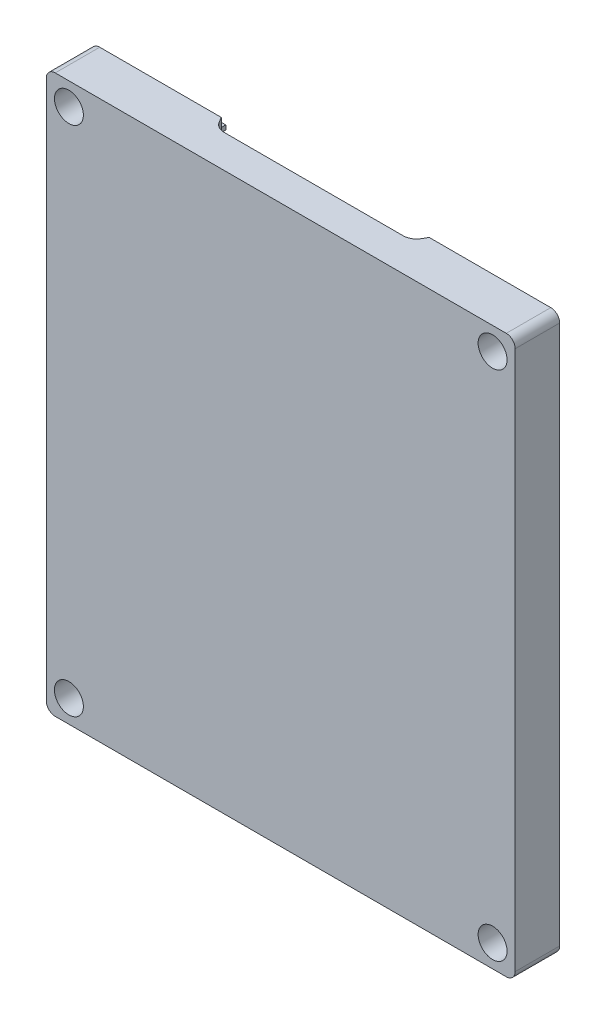
SolidWorks part; units mm, degrees
note: The reader was unsure of these and kept them because the rebuilt part matched: shared geometry of "Esquisse1<5>".
material "ABS"
ref_plane "Plan de face" through (0, 0, 0) normal (0, 0, 1) x (1, 0, 0)
ref_plane "Plan de dessus" through (0, 0, 0) normal (0, 1, 0) x (1, 0, 0)
ref_plane "Plan de droite" through (0, 0, 0) normal (1, 0, 0) x (0, 0, -1)
sketch "Esquisse1" plane through (0, 0, 0) normal (0, 0, 1) x (1, 0, 0)
  line L10 (-50.67, 60.555) -> (50.67, 60.555)
  line L11 (38.72, 58.605) -> (-38.72, 58.605)
  line L12 (-49.72, 46.1908) -> (-38.3058, 57.605)
  line L13 (38.3058, 57.605) -> (-38.3058, 57.605)
  line L14 (38.3058, 57.605) -> (49.72, 46.1908)
  line L15 (49.72, 46.1908) -> (49.72, -50.2908)
  line L21 (49.72, -50.2908) -> (38.3058, -61.705)
  line L26 (38.3058, -61.705) -> (-38.3058, -61.705)
  line L28 (-38.3058, -61.705) -> (-49.72, -50.2908)
  line L48 (-49.72, -50.2908) -> (-49.72, 46.1908)
  line L55 (-23.35, 60.555) -> (-50.67, 60.555)
  line L56 (-52.67, 58.555) -> (-52.67, -62.655)
  line L57 (-50.67, -64.655) -> (50.67, -64.655)
  line L58 (52.67, -62.655) -> (52.67, 58.555)
  line L59 (50.67, 60.555) -> (23.35, 60.555)
  line L64 (23.35, 60.555) -> (23.35, 58.605)
  line L65 (23.35, 58.605) -> (38.72, 58.605)
  line L66 (38.72, 58.605) -> (50.72, 46.605)
  line L67 (50.72, 46.605) -> (50.72, -50.705)
  line L68 (50.72, -50.705) -> (38.72, -62.705)
  line L69 (38.72, -62.705) -> (-38.72, -62.705)
  line L70 (-38.72, -62.705) -> (-50.72, -50.705)
  line L71 (-50.72, -50.705) -> (-50.72, 46.605)
  line L72 (-50.72, 46.605) -> (-38.72, 58.605)
  line L73 (-38.72, 58.605) -> (-23.35, 58.605)
  line L74 (-23.35, 58.605) -> (-23.35, 60.555)
  line L76 (-52.67, 58.555) -> (-52.67, -62.655)
  line L77 (-50.67, -64.655) -> (50.67, -64.655)
  line L78 (52.67, -62.655) -> (52.67, 58.555)
  line L82 (38.72, 58.605) -> (50.72, 46.605)
  line L83 (50.72, 46.605) -> (50.72, -50.705)
  line L84 (50.72, -50.705) -> (38.72, -62.705)
  line L85 (38.72, -62.705) -> (-38.72, -62.705)
  line L86 (-38.72, -62.705) -> (-50.72, -50.705)
  line L87 (-50.72, -50.705) -> (-50.72, 46.605)
  line L88 (-50.72, 46.605) -> (-38.72, 58.605)
  circle A1 centre (-47.5988, -59.5838) radius 1.6 construction
  circle A3 centre (47.5988, -59.5838) radius 1.6 construction
  arc A12 (-50.67, 60.555) -> (-52.67, 58.555) centre (-50.67, 58.555) ccw
  arc A13 (-52.67, -62.655) -> (-50.67, -64.655) centre (-50.67, -62.655) ccw
  arc A18 (50.67, -64.655) -> (52.67, -62.655) centre (50.67, -62.655) ccw
  arc A19 (52.67, 58.555) -> (50.67, 60.555) centre (50.67, 58.555) ccw
  arc A20 (-50.67, 60.555) -> (-52.67, 58.555) centre (-50.67, 58.555) ccw
  arc A21 (-52.67, -62.655) -> (-50.67, -64.655) centre (-50.67, -62.655) ccw
  arc A22 (50.67, -64.655) -> (52.67, -62.655) centre (50.67, -62.655) ccw
  arc A23 (52.67, 58.555) -> (50.67, 60.555) centre (50.67, 58.555) ccw
  circle A25 centre (47.5988, 55.4838) radius 1.6 construction
  circle A27 centre (-47.5988, 55.4838) radius 1.6 construction
  circle A29 centre (-47.5988, -59.5838) radius 1.6
  circle A31 centre (47.5988, -59.5838) radius 1.6
  circle A33 centre (47.5988, 55.4838) radius 1.6
  circle A35 centre (-47.5988, 55.4838) radius 1.6
  dimension "D1" = 0
  dimension "D2" = 1
extrude "Walls" add sketch "Esquisse1" along normal blind 10
extrude "Centrage" add sketch "Esquisse1<5>" against normal blind 1 contours L88 L87 L86 L85 L84 L83 L82 L11 L28 L48 L12 L13 L14 L15 L21 L26
sketch "Esquisse1<5>" plane through (0, 0, 0) normal (0, 0, 1) x (1, 0, 0) same geometry as "Esquisse1"
sketch "Esquisse2" plane through (0, 60.555, 0) normal (0, 1, 0) x (1, 0, 0)
  line L1 (-23.35, -2.6) -> (23.35, -2.6) construction
  line L2 (-23.35, -2.6) -> (-23.35, 1) construction
  line L3 (-23.35, 1) -> (23.35, 1)
  line L4 (23.35, -2.6) -> (23.35, 1) construction
  line L6 (-23.35, 0) -> (-22.72, -1.1)
  line L7 (-38.72, 0) -> (38.72, 0) construction
  line L8 (-23.35, 0) -> (-23.35, 1)
  line L9 (0, -55) -> (0, 55) construction
  line L10 (23.35, 0) -> (22.72, -1.1)
  line L11 (23.35, 0) -> (23.35, 1)
  line L12 (-20.12, -2.6) -> (20.12, -2.6)
  line L13 (-50.67, 0) -> (50.67, 0) construction
  line L20 (38.72, 1) -> (-38.72, 1) construction
  arc A0 (-22.72, -1.1) -> (-20.12, -2.6) centre (-20.1219, 0.4) ccw
  arc A1 (22.72, -1.1) -> (20.12, -2.6) centre (20.1219, 0.4) cw
  point P4 (23.35, 1)
  point P5 (0, 0)
  point P6 (0, -2.6)
  point P22 (0, 0)
  point P23 (0, 0)
  point P24 (23.35, 1)
  point P25 (-23.35, 1)
  point P28 (-23.35, 1)
  point P29 (0, 0)
  point P30 (0, 0)
  point P31 (0, 0)
  point P32 (0, 0)
  point P33 (0, 0)
  point P34 (0, 0)
  point P35 (0, 0)
  point P36 (0, 0)
  point P37 (0, 0)
  point P38 (0, 0)
  point P39 (0, 0)
  dimension "D5" = 3
  dimension "D1" = 46.7
  dimension "D2" = 2.6
  dimension "D3" = 1.1
  dimension "D4" = 0.63
  dimension "D6" = 3.23
extrude "Passage_CMC" cut sketch "Esquisse2" against normal up to next
sketch "Esquisse4" plane through (0, 0, 10) normal (0, 0, 1) x (1, 0, 0)
  line L8 (-49.72, -50.2908) -> (-49.72, 46.1908)
  line L9 (-38.3058, -61.705) -> (-49.72, -50.2908)
  line L10 (38.3058, -61.705) -> (-38.3058, -61.705)
  line L11 (49.72, -50.2908) -> (38.3058, -61.705)
  line L12 (49.72, 46.1908) -> (49.72, -50.2908)
  line L13 (38.3058, 57.605) -> (49.72, 46.1908)
  line L14 (-38.3058, 57.605) -> (38.3058, 57.605)
  line L15 (-49.72, 46.1908) -> (-38.3058, 57.605)
  line L16 (-49.72, -50.2908) -> (-49.72, 46.1908) construction
  line L17 (-49.72, 46.1908) -> (-38.3058, 57.605) construction
  point P3 (38.3058, -61.705)
  point P5 (-38.3058, -61.705)
  point P7 (-49.72, -50.2908)
  point P9 (-49.72, -50.2908)
  point P16 (49.72, -50.2908)
  point P17 (-49.72, 46.1908)
  point P21 (-38.3058, 57.605)
  point P24 (0, 0)
  point P25 (49.72, 46.1908)
  point P27 (49.72, -50.2908)
  point P28 (38.3058, 57.605)
  point P30 (-38.3058, 57.605)
extrude "Couvercle" add sketch "Esquisse4" against normal blind 2
sketch "Esquisse5" plane through (0, 0, 10) normal (0, 0, 1) x (1, 0, 0)
  line L0 (-47.5988, 55.4838) -> (-47.5988, 60.555) construction
  line L2 (-47.5988, 55.4838) -> (-52.67, 55.4838) construction
  line L4 (-47.5988, 55.4838) -> (-44.0129, 51.8979) construction
  line L8 (-49.72, 46.1908) -> (-38.3058, 57.605) construction
  line L9 (-50.67, 60.555) -> (50.67, 60.555) construction
  line L10 (-52.67, 58.555) -> (-52.67, -62.655) construction
  line L11 (-47.5988, -59.5838) -> (-44.0129, -55.9979) construction
  line L12 (-38.3058, -61.705) -> (-49.72, -50.2908) construction
  line L13 (-47.5988, -59.5838) -> (-52.67, -59.5838) construction
  line L14 (-47.5988, -59.5838) -> (-47.5988, -64.655) construction
  line L15 (-50.67, -64.655) -> (50.67, -64.655) construction
  line L16 (0, -55) -> (0, 55) construction
  circle A0 centre (-47.5988, 55.4838) radius 1.6
  circle A5 centre (-47.5988, -59.5838) radius 1.6
  circle A6 centre (47.5988, 55.4838) radius 1.6
  circle A7 centre (47.5988, -59.5838) radius 1.6
  circle A8 centre (-47.5988, -59.5838) radius 3.25
  circle A9 centre (-47.5988, 55.4838) radius 3.25
  circle A10 centre (47.5988, 55.4838) radius 3.25
  circle A11 centre (47.5988, -59.5838) radius 3.25
  dimension "D1" = 3.2
  dimension "D2" = 6.5
extrude "Passage_M3" cut sketch "Esquisse5" against normal blind 5
